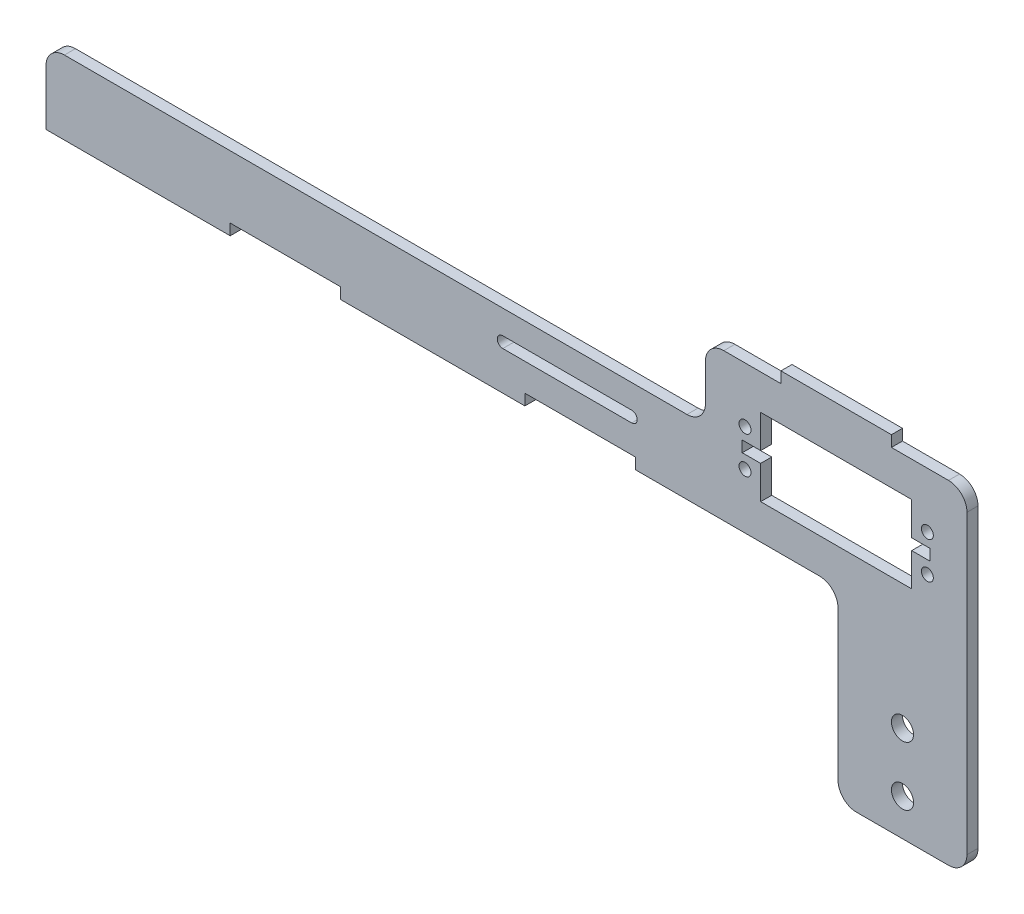
SolidWorks part; units mm, degrees
ref_plane "Plano frontal" through (0, 0, 0) normal (0, 0, 1) x (1, 0, 0)
ref_plane "Plano superior" through (0, 0, 0) normal (0, 1, 0) x (1, 0, 0)
ref_plane "Plano direito" through (0, 0, 0) normal (1, 0, 0) x (0, 0, -1)
sketch "Esboço1" plane through (0, 0, 0) normal (0, 0, 1) x (1, 0, 0)
  line L0 (194, 0) -> (235, 0) construction
  line L1 (215, -20) -> (160, -20)
  line L2 (250, -20) -> (250, 20)
  line L4 (0, -20) -> (0, 0)
  line L5 (194, 10.5) -> (235, 10.5)
  line L6 (194, 10.5) -> (194, -10.5)
  line L7 (194, -10.5) -> (235, -10.5)
  line L8 (235, 10.5) -> (235, -10.5)
  line L9 (214.5, 10.5) -> (214.5, -10.5) construction
  line L10 (0, 0) -> (179, 0)
  line L11 (179, 0) -> (179, 20)
  line L12 (250, 0) -> (184.4373, 0) construction
  line L13 (50, -20) -> (50, -17)
  line L14 (50, -17) -> (80, -17)
  line L15 (80, -17) -> (80, -20)
  line L16 (130, -20) -> (130, -17)
  line L17 (130, -17) -> (160, -17)
  line L18 (160, -17) -> (160, -20)
  line L19 (50, -20) -> (0, -20)
  line L20 (130, -20) -> (80, -20)
  line L21 (124, -8) -> (159, -8) construction
  line L22 (124, -6.5) -> (159, -6.5)
  line L23 (124, -9.5) -> (159, -9.5)
  line L26 (215, -20) -> (215, -70.5)
  line L27 (215, -70.5) -> (250, -70.5)
  line L28 (250, -20) -> (250, -70.5)
  line L29 (194, 1.5) -> (189, 1.5)
  line L30 (189, 1.5) -> (189, -1.5)
  line L31 (189, -1.5) -> (194, -1.5)
  line L32 (235, 1.5) -> (240, 1.5)
  line L33 (240, 1.5) -> (240, -1.5)
  line L34 (240, -1.5) -> (235, -1.5)
  line L36 (229.5, 23) -> (199.5, 23)
  line L37 (229.5, 23) -> (229.5, 20)
  line L38 (229.5, 20) -> (199.5, 20)
  line L39 (199.5, 23) -> (199.5, 20)
  line L40 (229.5, 23) -> (199.5, 20) construction
  line L41 (229.5, 20) -> (199.5, 23) construction
  line L42 (179, 20) -> (250, 20)
  circle A0 centre (189.75, 5) radius 1.625
  circle A1 centre (239.25, 5) radius 1.625
  circle A2 centre (239.25, -5) radius 1.625
  circle A3 centre (189.75, -5) radius 1.625
  arc A5 (124, -6.5) -> (124, -9.5) centre (124, -8) ccw
  arc A6 (159, -9.5) -> (159, -6.5) centre (159, -8) ccw
  circle A7 centre (232.5, -60.5) radius 3
  circle A8 centre (232.5, -44.5) radius 3
  point P36 (141.5, -8)
  point P51 (189, 0)
  point P52 (199.0456, 20)
  point P57 (214.5, 21.5)
  point P62 (214.5, 20)
  point P63 (215.9859, 21.5)
  point P64 (0, 0)
  dimension "D8" = 3.25
  dimension "D9" = 10
  dimension "D19" = 1.5
  dimension "D27" = 6
  dimension "D29" = 10
  dimension "D30" = 6
  dimension "D3" = 41
  dimension "D4" = 15
  dimension "D5" = 21
  dimension "D6" = 35
  dimension "D7" = 49.5
  dimension "D10" = 20
  dimension "D11" = 15
  dimension "D12" = 179
  dimension "D13" = 50
  dimension "D14" = 30
  dimension "D15" = 3
  dimension "D16" = 50
  dimension "D17" = 30
  dimension "D18" = 3
  dimension "D20" = 8
  dimension "D21" = 35
  dimension "D22" = 20
  dimension "D25" = 9.5
  dimension "D28" = 50.5
  dimension "D31" = 16
  dimension "D32" = 3
  dimension "D33" = 5
  dimension "D34" = 3
  dimension "D35" = 30
extrude "Ressalto-extrusão1" add sketch "Esboço1" along normal blind 3 contours L20 L16 L17 L18 L1 L2 L11 L10 L4 L19 L13 L14 L15 A1 A0 L5 L8 L7 L6 A2 A3 | L36 L39 L37 region at (158.2702, -15.7034, 0) region at (214.5, 21.5, 0)
fillet "Filete1" radius 5 7 edges at (215, -20, 1.5) (215, -70.5, 1.5) (250, -70.5, 1.5) (179, 0, 1.5) (0, 0, 1.5) (179, 20, 1.5) (250, 20, 1.5)
